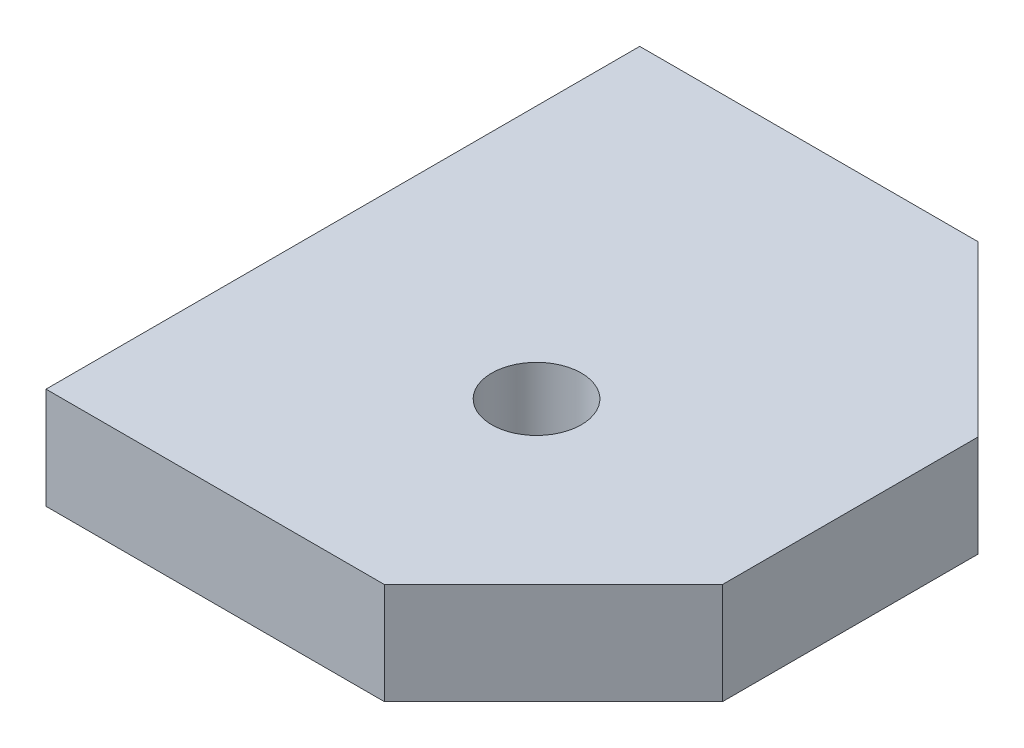
SolidWorks part; units mm, degrees
material "Maple"
ref_plane "Front Plane" through (0, 0, 0) normal (0, 0, 1) x (1, 0, 0)
ref_plane "Top Plane" through (0, 0, 0) normal (0, 1, 0) x (1, 0, 0)
ref_plane "Right Plane" through (0, 0, 0) normal (1, 0, 0) x (0, 0, -1)
sketch "Sketch1" plane through (0, 0, 0) normal (0, 1, 0) x (1, 0, 0)
  line L0 (93, 40.1) -> (48, 40.1) construction
  line L1 (0, 0) -> (30, 0)
  line L2 (0, 0) -> (0, 35.1)
  line L3 (0, 35.1) -> (30, 35.1)
  line L4 (30, 0) -> (30, 35.1)
  dimension "D1" = 5
  dimension "D2" = 30
extrude "Boss-Extrude1" add sketch "Sketch1" along normal blind 6
ref_plane "Plane1" through (0, 3, 0) normal (0, 1, 0) x (1, 0, 0)
chamfer "Chamfer1" distance 10 angle 45 2 edges at (30, 3, -35.1) (30, 3, 0)
hole_wizard "M5 Clearance Hole1" positions "Sketch3" profile "Sketch2" hole size "M5" standard "ANSI Metric" end condition through all
sketch "Sketch3" plane through (0, 0, 0) normal (0, -1, 0) x (-1, 0, 0)
  point P0 (-15, 14)
sketch "Sketch2" plane through (15, 0, -14) normal (1, 0, 0) x (0, 0, -1)
  line L0 (0, 0) -> (0, 6)
  line L1 (0, 6) -> (2.65, 6)
  line L2 (2.65, 6) -> (2.65, 0)
  line L5 (2.65, 0) -> (0, 0)
  line L11 (0, -6.35) -> (0, 107.95) construction
  dimension "Thru Hole Dia." = 5.3
  dimension "Thru Hole Depth" = 6
